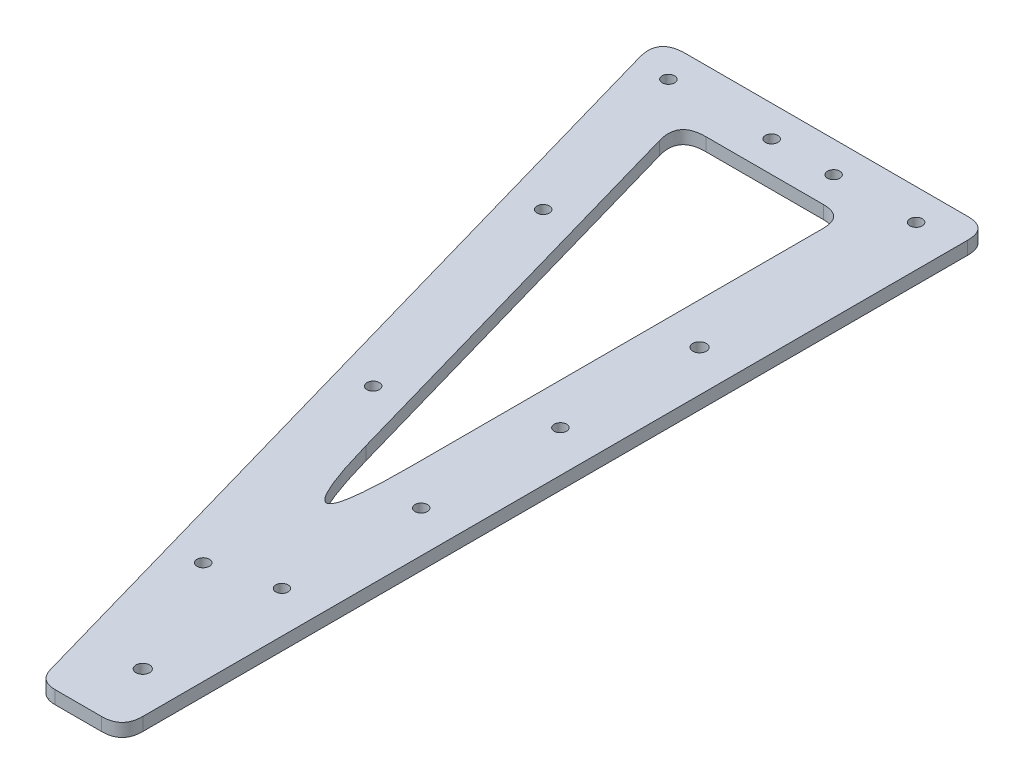
SolidWorks part; units mm, degrees
ref_plane "Front" through (0, 0, 0) normal (0, 0, 1) x (1, 0, 0)
ref_plane "Top" through (0, 0, 0) normal (0, 1, 0) x (1, 0, 0)
ref_plane "Right" through (0, 0, 0) normal (1, 0, 0) x (0, 0, -1)
sketch "Sketch1" plane through (0, 0, 0) normal (0, 1, 0) x (1, 0, 0)
  line L0 (-20, -210) -> (-80, 0)
  line L1 (0, 0) -> (-20, 0)
  line L2 (0, 0) -> (0, -210)
  line L3 (0, -210) -> (-20, -210)
  line L4 (-20, 0) -> (-20, -210)
  line L5 (-80, 0) -> (-20, 0)
  line L6 (-10, -210) -> (-10, -195)
  line L7 (-10, -195) -> (-10, -60)
  line L8 (-12.7886, -207.9396) -> (-70.057, -7.5)
  line L9 (-70.057, -7.5) -> (-20, -7.5)
  line L10 (-5.5771, -205.8792) -> (-60.1141, -15)
  line L11 (-60.1141, -15) -> (-20, -15)
  circle A0 centre (-10, -195) radius 1.65
  circle A1 centre (-10, -60) radius 1.65
  circle A2 centre (-70.057, -7.5) radius 1.5
  circle A3 centre (-45.0285, -7.5) radius 1.5
  circle A5 centre (-10, -127.5) radius 1500
  circle A6 centre (-10, -7.5) radius 1.5
  circle A7 centre (-10, -127.5) radius 1.5
  circle A8 centre (-10, -161.25) radius 1.5
  circle A9 centre (-10, -93.75) radius 1.5
  circle A10 centre (-41.4228, -107.7198) radius 1.5
  circle A11 centre (-57.9061, -50.0284) radius 1.5
  circle A12 centre (-24.9395, -165.4112) radius 1.5
  circle A13 centre (-30, -7.5) radius 1.5
  dimension "D6" = 7.5
  dimension "D7" = 33.75
  dimension "D10" = 60
  dimension "D1" = 20
  dimension "D2" = 210
  dimension "D3" = 60
  dimension "D4" = 15
  dimension "D5" = 135
  dimension "D8" = 33.75
  dimension "D11" = 60
  dimension "D12" = 10
  dimension "D9" = 15
extrude "Boss-Extrude1" add sketch "Sketch1" along normal blind 3.175
fillet "Fillet1" radius 5 7 edges at (-20, 1.5875, 15) (-60.1141, 1.5875, 15) (-80, 1.5875, 0) (0, 1.5875, 0) (0, 1.5875, 210) (-20, 1.5875, 210) (-20, 1.5875, 155.3992)
